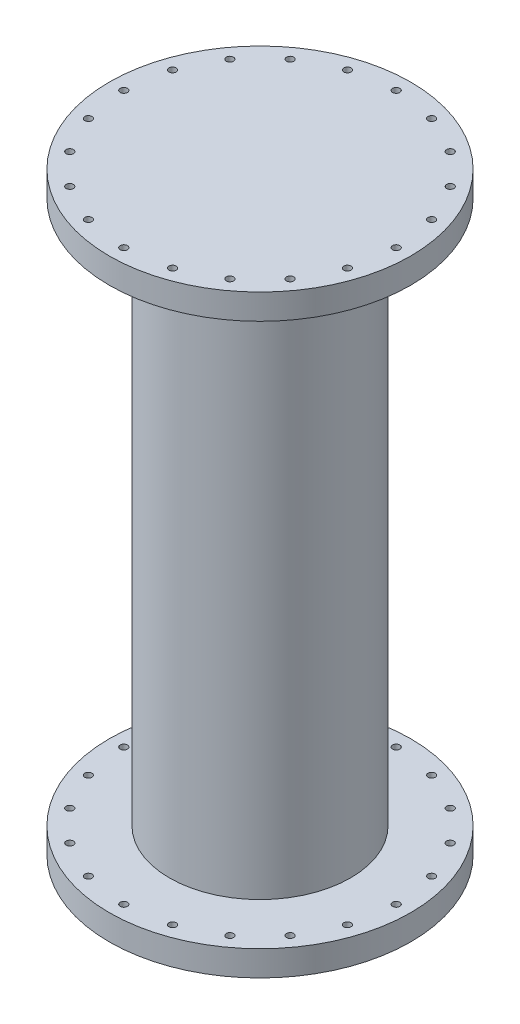
SolidWorks part; units mm, degrees
ref_plane "Plan de face" through (0, 0, 0) normal (0, 0, 1) x (1, 0, 0)
ref_plane "Plan de dessus" through (0, 0, 0) normal (0, 1, 0) x (1, 0, 0)
ref_plane "Plan de droite" through (0, 0, 0) normal (1, 0, 0) x (0, 0, -1)
sketch "Esquisse1" plane through (0, 0, 0) normal (0, 0, 1) x (1, 0, 0)
  line L0 (0, 0) -> (0, -1756.5308) construction
  line L1 (0, 0) -> (416, 0)
  line L2 (0, 0) -> (0, -70)
  line L3 (0, -70) -> (200, -70)
  line L4 (416, 0) -> (416, -70)
  line L26 (250, -70) -> (416, -70)
  line L27 (250, -1570) -> (416, -1570)
  line L29 (200, -70) -> (200, -1570)
  line L31 (250, -70) -> (250, -1570)
  line L32 (0, -1570) -> (200, -1570)
  line L33 (0, -1570) -> (0, -1640)
  line L34 (0, -1640) -> (416, -1640)
  line L35 (416, -1570) -> (416, -1640)
  dimension "D1" = 416
  dimension "D2" = 70
  dimension "D3" = 70
  dimension "D4" = 416
  dimension "D5" = 250
  dimension "D6" = 200
  dimension "D7" = 1500
revolve "Révolution1" add sketch "Esquisse1" angle 360 about L0
sketch "Esquisse2" plane through (0, 0, 0) normal (0, 1, 0) x (1, 0, 0)
  circle A0 centre (376, 0) radius 10
  dimension "D2" = 20
  dimension "D1" = 376
extrude "Enlèv. mat.-Extru.1" cut sketch "Esquisse2" against normal through all
pattern_circular "Répétition circulaire1" count 20 over 360 about axis through (0, 0, 0) along (0, 1, 0) of "Enlèv. mat.-Extru.1"
